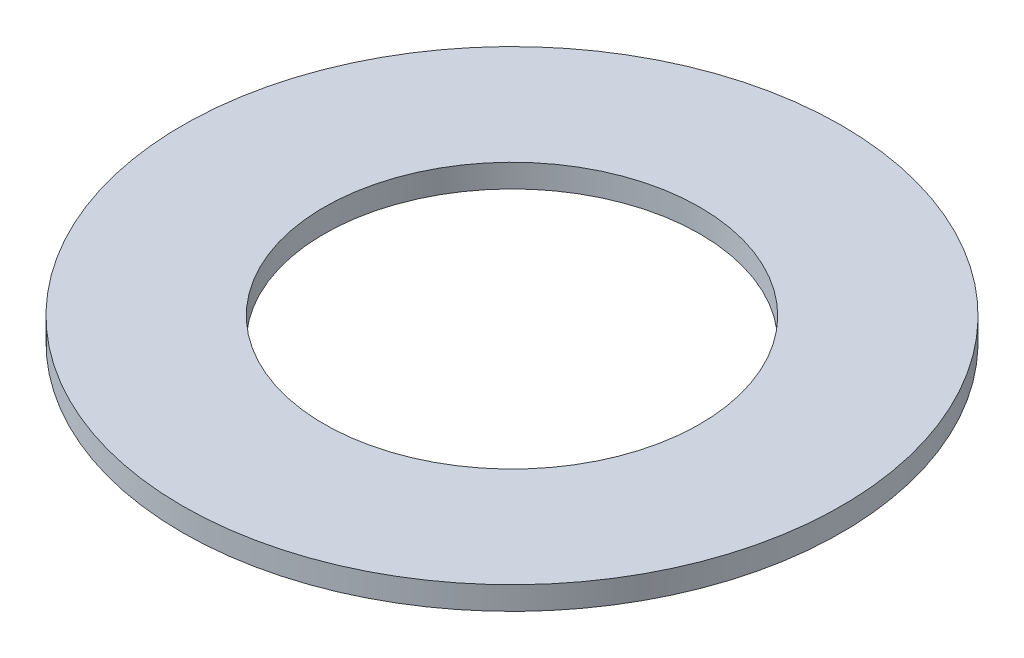
SolidWorks part; units mm, degrees
material "Polyetheretherketone (PEEK)"
ref_plane "Front Plane" through (0, 0, 0) normal (0, 0, 1) x (1, 0, 0)
ref_plane "Top Plane" through (0, 0, 0) normal (0, 1, 0) x (1, 0, 0)
ref_plane "Right Plane" through (0, 0, 0) normal (1, 0, 0) x (0, 0, -1)
sketch "Sketch1" plane through (0, 0, 0) normal (0, 0, 1) x (1, 0, 0)
  line L0 (0, 0) -> (0, 50000) construction
  line L2 (32.5, 2) -> (57, 2)
  line L3 (32.5, 2) -> (32.5, -2)
  line L4 (32.5, -2) -> (57, -2)
  line L5 (57, 2) -> (57, -2)
  point P7 (57, 0)
  dimension "D1" = 114
  dimension "D2" = 65
  dimension "D3" = 4
revolve "Revolve1" add sketch "Sketch1" angle 360 about L0
equation "\"CanSat_Len\"= 400mm"
equation "\"CanSat_Dia\"= 150mm"
equation "\"BodyTube_ID\"= 114mm"
equation "\"BodyTube_OD\"= 120mm"
equation "\"PayLoadBay_ID\"= 164mm"
equation "\"PayLoadBay_OD\"= 170mm"
equation "\"ParachuteBay_Pitch\"= 300mm"
equation "\"ElectronicsTray_PitchDist\"= 40mm"
equation "\"ElectronicsTray_Height\"= 120mm"
equation "\"MotorDia\"= 98mm"
equation "\"MotorLen\"= 289mm"
equation "\"D1@Sketch1\"=\"BodyTube_ID\""
